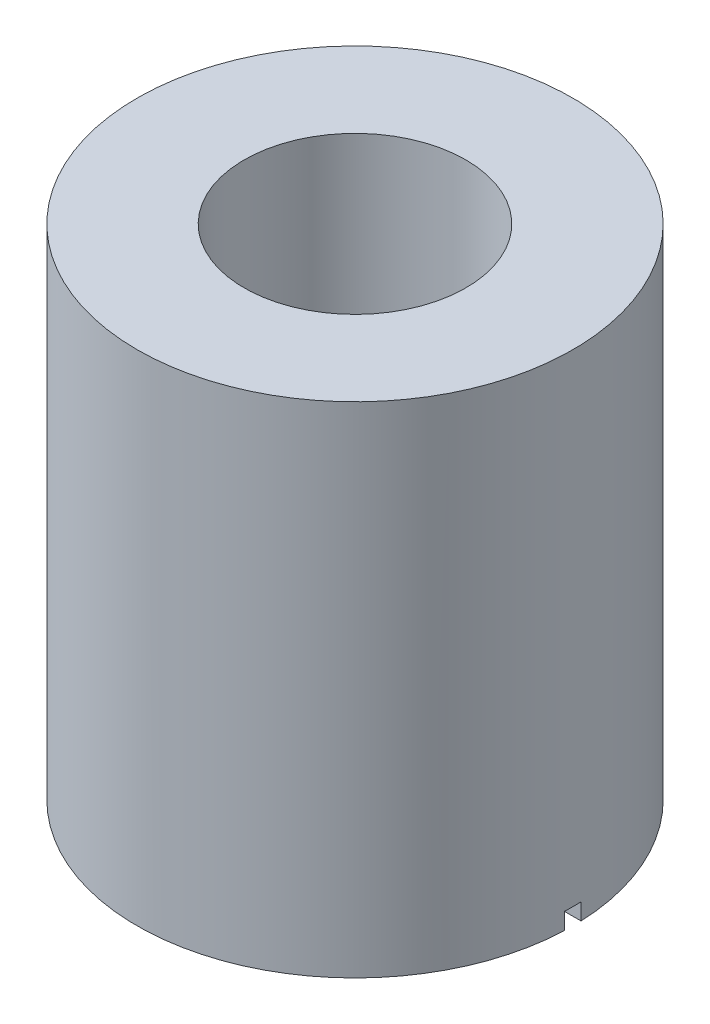
SolidWorks part; units mm, degrees
ref_plane "前视基准面" through (0, 0, 0) normal (0, 0, 1) x (1, 0, 0)
ref_plane "上视基准面" through (0, 0, 0) normal (0, 1, 0) x (1, 0, 0)
ref_plane "右视基准面" through (0, 0, 0) normal (1, 0, 0) x (0, 0, -1)
sketch "草图1" plane through (0, 0, 0) normal (0, 1, 0) x (1, 0, 0)
  circle A0 centre (0, 0) radius 19.65
  circle A1 centre (0, 0) radius 10
  dimension "D1" = 39.3
  dimension "D2" = 20
extrude "凸台-拉伸1" add sketch "草图1" along normal blind 45
sketch "草图2" plane through (0, 0, 0) normal (0, -1, 0) x (1, 0, 0)
  circle A0 centre (0, 0) radius 10
  circle A1 centre (0, 0) radius 0.5
  dimension "D1" = 20
  dimension "D2" = 1
extrude "凸台-拉伸2" add sketch "草图2" against normal blind 18
sketch "草图3" plane through (0, 0, 0) normal (0, -1, 0) x (1, 0, 0)
  circle A1 centre (0, 0) radius 16
  dimension "D2" = 32
extrude "切除-拉伸1" cut sketch "草图3" against normal blind 5
ref_axis "基准轴1" through (0, 45, 0) along (0, -1, 0)
sketch "草图4" plane through (0, 45, 0) normal (0, 1, 0) x (1, 0, 0)
  line L0 (0, 0) -> (-30.9859, 0) construction
ref_plane "基准面1" through (0, 45, 0) normal (-1, 0, 0) x (0, 0, 1)
sketch "草图5" plane through (0, 45, 0) normal (-1, 0, 0) x (0, 0, 1)
  line L1 (0.75, -43.5) -> (-0.75, -43.5)
  line L2 (0.75, -43.5) -> (0.75, -45)
  line L3 (0.75, -45) -> (-0.75, -45)
  line L4 (-0.75, -43.5) -> (-0.75, -45)
  dimension "D1" = 1.5
  dimension "D2" = 1.5
extrude "切除-拉伸2" cut sketch "草图5" against normal mid plane 127
